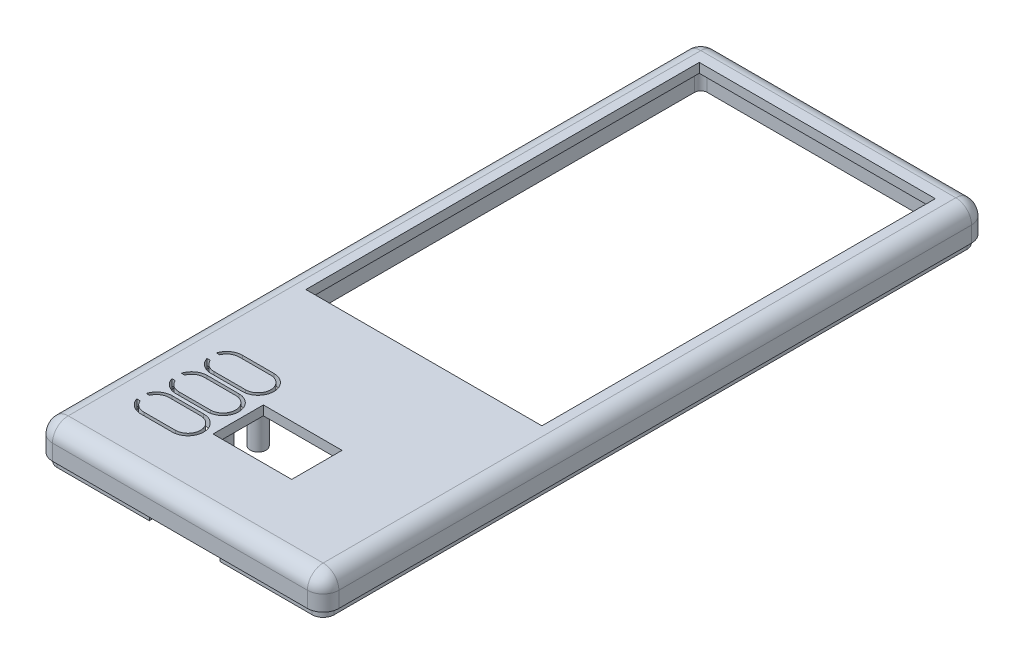
SolidWorks part; units mm, degrees
ref_plane "Front Plane" through (0, 0, 0) normal (0, 0, 1) x (1, 0, 0)
ref_plane "Top Plane" through (0, 0, 0) normal (0, 1, 0) x (1, 0, 0)
ref_plane "Right Plane" through (0, 0, 0) normal (1, 0, 0) x (0, 0, -1)
sketch "Sketch1" plane through (0, 0, 0) normal (0, 1, 0) x (1, 0, 0)
  line L1 (-45.5, -105.5) -> (45.5, -105.5)
  line L2 (-45.5, -105.5) -> (-45.5, 105.5)
  line L3 (-45.5, 105.5) -> (45.5, 105.5)
  line L4 (45.5, -105.5) -> (45.5, 105.5)
  line L5 (-45.5, -105.5) -> (45.5, 105.5) construction
  line L6 (-45.5, 105.5) -> (45.5, -105.5) construction
  point P0 (0, 0)
  dimension "D1" = 91
  dimension "D2" = 211
extrude "Boss-Extrude1" add sketch "Sketch1" along normal blind 3
fillet "Fillet1" radius 5 4 edges at (45.5, 1.5, -105.5) (-45.5, 1.5, -105.5) (-45.5, 1.5, 105.5) (45.5, 1.5, 105.5)
sketch "Sketch2" plane through (0, 0, 0) normal (0, -1, 0) x (1, 0, 0)
  line L28 (-40.5, 105.5) -> (40.5, 105.5) construction
  line L29 (-40.5, -105.5) -> (40.5, -105.5)
  line L30 (-45.5, -100.5) -> (-45.5, 100.5)
  line L31 (-40.5, 105.5) -> (40.5, 105.5)
  line L32 (45.5, -100.5) -> (45.5, 100.5)
  line L33 (-45.5, -105.5) -> (45.5, 105.5) construction
  line L34 (-45.5, 105.5) -> (45.5, -105.5) construction
  line L35 (45.5, 100.5) -> (45.5, -100.5) construction
  line L36 (-42.5, -100.5) -> (-42.5, 100.5)
  line L37 (-40.5, 102.5) -> (40.5, 102.5)
  line L38 (42.5, -100.5) -> (42.5, 100.5)
  line L39 (-40.5, -102.5) -> (40.5, -102.5)
  arc A28 (40.5, -105.5) -> (45.5, -100.5) centre (40.5, -100.5) ccw
  arc A29 (-40.5, -105.5) -> (-45.5, -100.5) centre (-40.5, -100.5) cw
  arc A30 (40.5, 105.5) -> (45.5, 100.5) centre (40.5, 100.5) cw
  arc A31 (-45.5, 100.5) -> (-40.5, 105.5) centre (-40.5, 100.5) cw
  arc A32 (-42.5, 100.5) -> (-40.5, 102.5) centre (-40.5, 100.5) cw
  arc A33 (40.5, 102.5) -> (42.5, 100.5) centre (40.5, 100.5) cw
  arc A34 (40.5, -102.5) -> (42.5, -100.5) centre (40.5, -100.5) ccw
  arc A35 (-40.5, -102.5) -> (-42.5, -100.5) centre (-40.5, -100.5) cw
  point P0 (0, 0)
  point P9 (0, 0)
  dimension "D1" = 5
  dimension "D2" = 3
extrude "Boss-Extrude2" add sketch "Sketch2" along normal blind 7
sketch "Sketch3" plane through (0, 0, 0) normal (0, -1, 0) x (1, 0, 0)
  line L1 (-37.5, 28) -> (37.5, 28)
  line L2 (-37.5, 28) -> (-37.5, -97)
  line L3 (-37.5, -97) -> (37.5, -97)
  line L4 (37.5, 28) -> (37.5, -97)
  line L5 (-37.5, 28) -> (37.5, -97) construction
  line L6 (-37.5, -97) -> (37.5, 28) construction
  line L8 (-12.5, 66.5) -> (12.5, 66.5)
  line L9 (-12.5, 66.5) -> (-12.5, 82.5)
  line L10 (-12.5, 82.5) -> (12.5, 82.5)
  line L11 (12.5, 66.5) -> (12.5, 82.5)
  line L12 (-12.5, 66.5) -> (12.5, 82.5) construction
  line L13 (-12.5, 82.5) -> (12.5, 66.5) construction
  line L15 (40.5, 105.5) -> (-40.5, 105.5) construction
  line L16 (-40.5, -105.5) -> (40.5, -105.5) construction
  point P0 (0, -34.5)
  point P5 (0, 0)
  point P9 (0, 74.5)
  dimension "D1" = 75
  dimension "D2" = 125
  dimension "D3" = 71
  dimension "D4" = 25
  dimension "D5" = 16
  dimension "D6" = 31
extrude "Cut-Extrude1" cut sketch "Sketch3" against normal up to next
sketch "Sketch4" plane through (0, 0, 0) normal (0, -1, 0) x (1, 0, 0)
  line L0 (-19.5, 83.45) -> (-19.5, 61.15) construction
  line L4 (-45.5, 100.5) -> (-45.5, -100.5) construction
  line L5 (40.5, 105.5) -> (-40.5, 105.5) construction
  circle A0 centre (-19.5, 83.45) radius 2.5
  circle A1 centre (-19.5, 61.15) radius 2.5
  circle A2 centre (-19.5, 72.3) radius 2.5
  dimension "D4" = 5
  dimension "D5" = 5
  dimension "D6" = 5
  dimension "D1" = 26
  dimension "D2" = 33.2
  dimension "D3" = 22.3
extrude "Boss-Extrude3" add sketch "Sketch4" along normal blind 14.4
sketch "Sketch5" plane through (0, 0, 0) normal (0, -1, 0) x (1, 0, 0)
  line L2 (-19.5, 87.45) -> (-29.5, 87.45)
  line L4 (-19.5, 79.45) -> (-29.5, 79.45)
  line L6 (-19.5, 88.45) -> (-29.5, 88.45)
  line L8 (-29.5454, 78.45) -> (-19.5, 78.45)
  line L23 (-34.2698, 84.95) -> (-33.2082, 84.95)
  line L24 (-34.2698, 81.95) -> (-33.208, 81.95)
  line L25 (-19.5, 83.45) -> (-19.5, 61.15) construction
  line L27 (-19.5, 76.3) -> (-29.5, 76.3)
  line L28 (-19.5, 68.3) -> (-29.5, 68.3)
  line L29 (-19.5, 77.3) -> (-29.5, 77.3)
  line L30 (-29.5454, 67.3) -> (-19.5, 67.3)
  line L31 (-34.2698, 73.8) -> (-33.2082, 73.8)
  line L32 (-34.2698, 70.8) -> (-33.208, 70.8)
  line L33 (-19.5, 65.15) -> (-29.5, 65.15)
  line L34 (-19.5, 57.15) -> (-29.5, 57.15)
  line L35 (-19.5, 66.15) -> (-29.5, 66.15)
  line L36 (-29.5454, 56.15) -> (-19.5, 56.15)
  line L37 (-34.2698, 62.65) -> (-33.2082, 62.65)
  line L38 (-34.2698, 59.65) -> (-33.208, 59.65)
  line L39 (-19.5, 87.45) -> (-19.5, 76.3) construction
  arc A2 (-19.5, 79.45) -> (-19.5, 87.45) centre (-19.5, 83.45) ccw
  arc A3 (-19.5, 78.45) -> (-19.5, 88.45) centre (-19.5, 83.45) ccw
  arc A8 (-33.208, 81.95) -> (-29.5, 79.45) centre (-29.5, 83.4499) ccw
  arc A9 (-34.2698, 81.95) -> (-29.5454, 78.45) centre (-29.5, 83.4499) ccw
  arc A10 (-29.5, 88.45) -> (-34.2698, 84.95) centre (-29.5, 83.4499) ccw
  arc A11 (-29.5, 87.45) -> (-33.2082, 84.95) centre (-29.5, 83.4499) ccw
  arc A12 (-19.5, 68.3) -> (-19.5, 76.3) centre (-19.5, 72.3) ccw
  arc A13 (-19.5, 67.3) -> (-19.5, 77.3) centre (-19.5, 72.3) ccw
  arc A14 (-33.208, 70.8) -> (-29.5, 68.3) centre (-29.5, 72.2999) ccw
  arc A15 (-34.2698, 70.8) -> (-29.5454, 67.3) centre (-29.5, 72.2999) ccw
  arc A16 (-29.5, 77.3) -> (-34.2698, 73.8) centre (-29.5, 72.2999) ccw
  arc A17 (-29.5, 76.3) -> (-33.2082, 73.8) centre (-29.5, 72.2999) ccw
  arc A18 (-19.5, 57.15) -> (-19.5, 65.15) centre (-19.5, 61.15) ccw
  arc A19 (-19.5, 56.15) -> (-19.5, 66.15) centre (-19.5, 61.15) ccw
  arc A20 (-33.208, 59.65) -> (-29.5, 57.15) centre (-29.5, 61.1499) ccw
  arc A21 (-34.2698, 59.65) -> (-29.5454, 56.15) centre (-29.5, 61.1499) ccw
  arc A22 (-29.5, 66.15) -> (-34.2698, 62.65) centre (-29.5, 61.1499) ccw
  arc A23 (-29.5, 65.15) -> (-33.2082, 62.65) centre (-29.5, 61.1499) ccw
  dimension "D1" = 8
  dimension "D5" = 2.5
  dimension "D7" = 3.9999
  dimension "D3" = 1
  dimension "D4" = 2.5
  dimension "D6" = 10
  dimension "D2" = 10
  dimension "D8" = 11.15
extrude "Cut-Extrude4" cut sketch "Sketch5" against normal up to next
sketch "Sketch7" plane through (0, 0, 0) normal (0, -1, 0) x (1, 0, 0)
  line L1 (-33.2082, 84.95) -> (-34.2698, 84.95)
  line L2 (-33.2082, 84.95) -> (-33.2082, 81.95)
  line L3 (-33.2082, 81.95) -> (-34.2698, 81.95)
  line L4 (-34.2698, 84.95) -> (-34.2698, 81.95)
  line L5 (-33.2082, 73.8) -> (-34.2698, 73.8)
  line L6 (-33.2082, 73.8) -> (-33.2082, 70.8)
  line L7 (-33.2082, 70.8) -> (-34.2698, 70.8)
  line L8 (-34.2698, 73.8) -> (-34.2698, 70.8)
  line L9 (-33.2082, 62.65) -> (-34.2698, 62.65)
  line L10 (-33.2082, 62.65) -> (-33.2082, 59.65)
  line L11 (-33.2082, 59.65) -> (-34.2698, 59.65)
  line L12 (-34.2698, 62.65) -> (-34.2698, 59.65)
extrude "Cut-Extrude5" cut sketch "Sketch7" against normal blind 1
sketch "Sketch8" plane through (0, -7, 0) normal (0, -1, 0) x (1, 0, 0)
  line L0 (40.5, 102.5) -> (-40.5, 102.5) construction
  line L1 (42.5, -100.5) -> (42.5, 100.5) construction
  line L2 (-42.5, 100.5) -> (-42.5, -100.5) construction
  line L3 (-40.5, -102.5) -> (40.5, -102.5) construction
  line L4 (40.5, 102.5) -> (-40.5, 102.5)
  line L5 (42.5, -100.5) -> (42.5, 100.5)
  line L6 (-42.5, 100.5) -> (-42.5, -100.5)
  line L7 (-40.5, -102.5) -> (40.5, -102.5)
  line L8 (-44, 100.5) -> (-44, -100.5)
  line L9 (-40.5, -104) -> (40.5, -104)
  line L10 (44, -100.5) -> (44, 100.5)
  line L11 (40.5, 104) -> (-40.5, 104)
  arc A0 (-40.5, 102.5) -> (-42.5, 100.5) centre (-40.5, 100.5) ccw construction
  arc A1 (42.5, 100.5) -> (40.5, 102.5) centre (40.5, 100.5) ccw construction
  arc A2 (40.5, -102.5) -> (42.5, -100.5) centre (40.5, -100.5) ccw construction
  arc A3 (-42.5, -100.5) -> (-40.5, -102.5) centre (-40.5, -100.5) ccw construction
  arc A4 (-40.5, 102.5) -> (-42.5, 100.5) centre (-40.5, 100.5) ccw
  arc A5 (42.5, 100.5) -> (40.5, 102.5) centre (40.5, 100.5) ccw
  arc A6 (40.5, -102.5) -> (42.5, -100.5) centre (40.5, -100.5) ccw
  arc A7 (-42.5, -100.5) -> (-40.5, -102.5) centre (-40.5, -100.5) ccw
  arc A8 (-40.5, 104) -> (-44, 100.5) centre (-40.5, 100.5) ccw
  arc A9 (-44, -100.5) -> (-40.5, -104) centre (-40.5, -100.5) ccw
  arc A10 (40.5, -104) -> (44, -100.5) centre (40.5, -100.5) ccw
  arc A11 (44, 100.5) -> (40.5, 104) centre (40.5, 100.5) ccw
  dimension "D1" = 1.5
extrude "Boss-Extrude4" add sketch "Sketch8" along normal blind 2.5
fillet "Fillet2" radius 5 8 edges at (44.0355, 3, 104.0355) (0, 3, 105.5) (-44.0355, 3, 104.0355) (-45.5, 3, 0) (-44.0355, 3, -104.0355) (0, 3, -105.5) (44.0355, 3, -104.0355) (45.5, 3, 0)
sketch "Sketch9" plane through (0, 0, 105.5) normal (0, 0, 1) x (1, 0, 0)
  line L0 (40.5, -9.5) -> (-40.5, -9.5) construction
  line L1 (-11.25, -7) -> (11.25, -7)
  line L2 (-11.25, -7) -> (-11.25, -9.5)
  line L3 (-11.25, -9.5) -> (11.25, -9.5)
  line L4 (11.25, -7) -> (11.25, -9.5)
  line L5 (-11.25, -7) -> (11.25, -9.5) construction
  line L6 (-11.25, -9.5) -> (11.25, -7) construction
  line L7 (40.5, -7) -> (-40.5, -7) construction
  point P0 (0, -8.25)
  point P5 (0, 0)
  dimension "D1" = 22.5
extrude "Cut-Extrude6" cut sketch "Sketch9" against normal up to next
